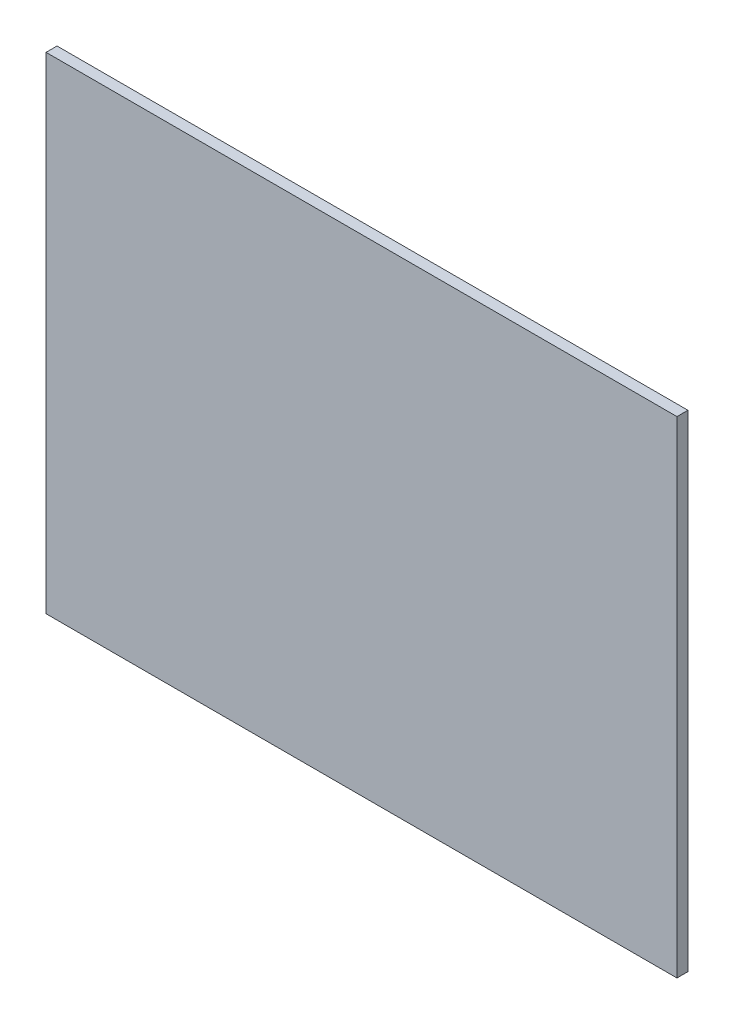
SolidWorks part; units mm, degrees
ref_plane "Front Plane" through (0, 0, 0) normal (0, 0, 1) x (1, 0, 0)
ref_plane "Top Plane" through (0, 0, 0) normal (0, 1, 0) x (1, 0, 0)
ref_plane "Right Plane" through (0, 0, 0) normal (1, 0, 0) x (0, 0, -1)
sketch "Sketch1" plane through (0, 0, 0) normal (0, 0, 1) x (1, 0, 0)
  line L1 (-49.2269, 40.15) -> (59.7731, 40.15)
  line L2 (-49.2269, 40.15) -> (-49.2269, -43.85)
  line L3 (-49.2269, -43.85) -> (59.7731, -43.85)
  line L4 (59.7731, 40.15) -> (59.7731, -43.85)
  dimension "D1" = 109
  dimension "D2" = 84
base flange "Base-Flange1" sketch "Sketch1" thickness 1.8974 reverse thickness direction no parameters "D1"=2.54
sketch "Bend-Lines1" plane through (0, 0, 0) normal (0, 1, 0) x (1, 0, 0)
sketch "Bounding-Box1" plane through (0, 0, 0) normal (0, 1, 0) x (1, 0, 0)
sheet metal parameters "Sheet-Metal1" thickness 1.8974 parameters "D1"=2.54
flat pattern "Flat-Pattern1" [suppressed]
sketch "Bend-Lines2" plane through (0, 0, 0) normal (0, 1, 0) x (1, 0, 0)
sketch "Bounding-Box2" [suppressed] plane through (0, 0, 0) normal (0, 1, 0) x (1, 0, 0)
